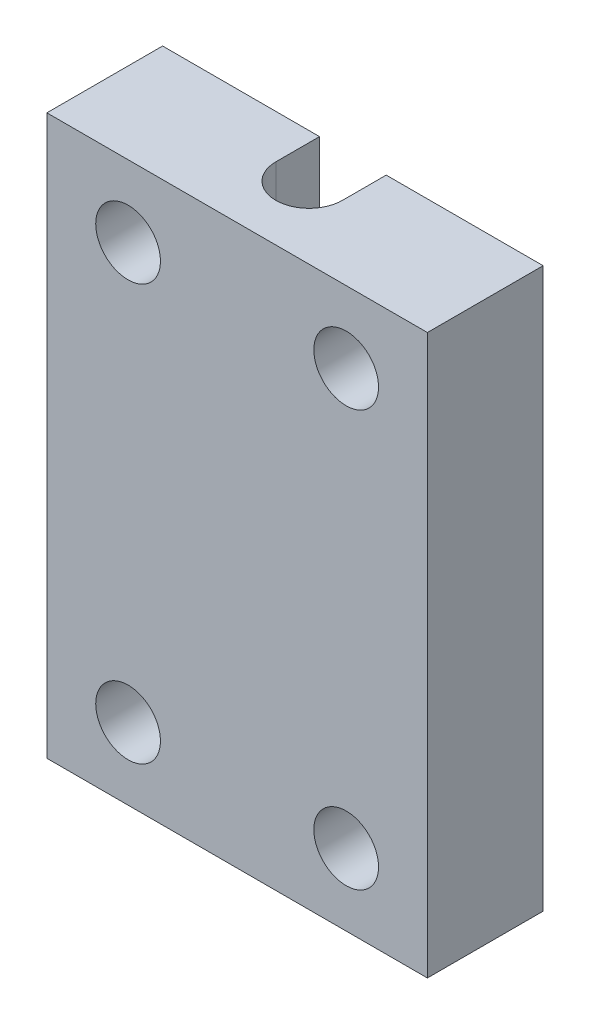
SolidWorks part; units mm, degrees
ref_plane "Front Plane" through (0, 0, 0) normal (0, 0, 1) x (1, 0, 0)
ref_plane "Top Plane" through (0, 0, 0) normal (0, 1, 0) x (1, 0, 0)
ref_plane "Right Plane" through (0, 0, 0) normal (1, 0, 0) x (0, 0, -1)
sketch "Sketch1" plane through (0, 0, 0) normal (0, 1, 0) x (1, 0, 0)
  line L0 (-9.7, 0) -> (-1.7, 0)
  line L1 (-9.7, 0) -> (-9.7, -5.9)
  line L2 (9.7, -5.9) -> (9.7, 0)
  line L19 (1.7, 0) -> (9.7, 0)
  line L21 (-1.7, -2.23) -> (-1.7, 0)
  line L27 (1.7, -2.23) -> (1.7, 0)
  line L28 (-9.7, -5.9) -> (9.7, -5.9)
  arc A2 (-1.7, -2.23) -> (1.7, -2.23) centre (0, -2.23) ccw
extrude "Boss-Extrude1" add sketch "Sketch1" along normal blind 28.5
sketch "Sketch2" plane through (0, 0, 0) normal (0, 0, -1) x (-1, 0, 0)
  circle A1 centre (5.56, 24.8442) radius 1.65
  circle A2 centre (5.56, 3.6558) radius 1.65
  circle A3 centre (-5.56, 3.6558) radius 1.65
  circle A4 centre (-5.56, 24.8442) radius 1.65
extrude "Cut-Extrude1" cut sketch "Sketch2" against normal up to surface (5.9 mm away) up to face at (0, 14.25, 5.9)
sketch "Sketch4" plane through (0, 0, 0) normal (0, 0, -1) x (-1, 0, 0)
  line L7 (1.7, 17.4013) -> (1.7, 16.3683)
  line L9 (-1.7, 17.4013) -> (-1.7, 16.3683)
  line L12 (1.7, 12.5317) -> (1.7, 11.4987)
  line L13 (-1.7, 12.5317) -> (-1.7, 11.4987)
  arc A0 (-1.7593, 16.2262) -> (-1.7593, 12.6738) centre (0, 14.45) ccw
  arc A2 (1.7593, 12.6738) -> (1.7593, 16.2262) centre (0, 14.45) ccw
  arc A5 (1.7593, 12.6738) -> (1.7, 12.5317) centre (1.9, 12.5317) ccw
  arc A7 (-1.7593, 12.6738) -> (-1.7, 12.5317) centre (-1.9, 12.5317) cw
  arc A8 (-1.7593, 16.2262) -> (-1.7, 16.3683) centre (-1.9, 16.3683) ccw
  arc A10 (1.7, 16.3683) -> (1.7593, 16.2262) centre (1.9, 16.3683) ccw
  arc A12 (-2.0083, 17.5695) -> (-2.0083, 11.3305) centre (0, 14.45) ccw
  arc A13 (2.0083, 11.3305) -> (2.0083, 17.5695) centre (0, 14.45) ccw
  arc A14 (2.0083, 11.3305) -> (1.7, 11.4987) centre (1.9, 11.4987) cw
  arc A15 (-2.0083, 11.3305) -> (-1.7, 11.4987) centre (-1.9, 11.4987) ccw
  arc A16 (-2.0083, 17.5695) -> (-1.7, 17.4013) centre (-1.9, 17.4013) cw
  arc A17 (1.7, 17.4013) -> (2.0083, 17.5695) centre (1.9, 17.4013) cw
  point P2 (0, 0)
extrude "Boss-Extrude2" add sketch "Sketch4" along normal blind 0.5
sketch "Sketch5" plane through (0, 0, -0.5) normal (0, 0, -1) x (-1, 0, 0)
  circle A0 centre (0, 14.45) radius 2.5
extrude "Cut-Extrude3" cut sketch "Sketch5" against normal blind 3.5
